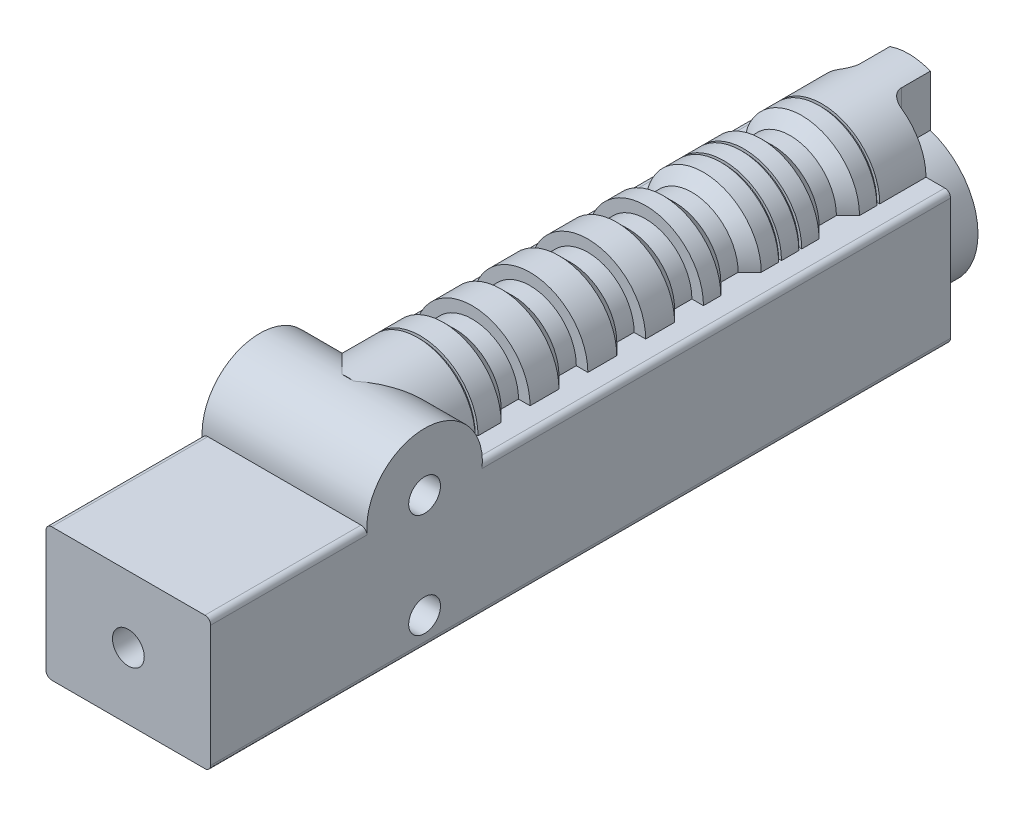
SolidWorks part; units mm, degrees
ref_plane "Front Plane" through (0, 0, 0) normal (0, 0, 1) x (1, 0, 0)
ref_plane "Top Plane" through (0, 0, 0) normal (0, 1, 0) x (1, 0, 0)
ref_plane "Right Plane" through (0, 0, 0) normal (1, 0, 0) x (0, 0, -1)
sketch "Sketch1" plane through (0, 0, 0) normal (0, 0, 1) x (1, 0, 0)
  line L1 (-14.25, -11.5) -> (14.25, -11.5)
  line L2 (-14.25, -11.5) -> (-14.25, 11.5)
  line L3 (-14.25, 11.5) -> (14.25, 11.5)
  line L4 (14.25, -11.5) -> (14.25, 11.5)
  line L5 (-14.25, -11.5) -> (14.25, 11.5) construction
  line L6 (-14.25, 11.5) -> (14.25, -11.5) construction
  point P0 (0, 0)
  dimension "D1" = 23
  dimension "D2" = 28.5
extrude "Centre block" add sketch "Sketch1" along normal blind 128
sketch "Sketch3" plane through (0, 0, 0) normal (0, 0, -1) x (-1, 0, 0)
  line L0 (-14.25, 11.5) -> (14.25, 11.5) construction
  line L1 (-10, 11.5) -> (10, 11.5)
  arc A0 (10, 11.5) -> (-10, 11.5) centre (0, 11.5) ccw
  dimension "D1" = 20
extrude "top cylinder" add sketch "Sketch3" against normal blind 90 and the other way blind 7
ref_plane "top" through (0, 11.5, 0) normal (0, 1, 0) x (1, 0, 0)
ref_axis "Axis3" through (0, 11.5, -7) along (0, 0, 1)
sketch "Sketch9" plane through (0, 11.5, 0) normal (0, 1, 0) x (1, 0, 0)
  line L0 (10, 0) -> (10, -90) construction
  line L1 (10, -78) -> (10, -81.8886)
  line L2 (10, -74.0526) -> (10, -73.5)
  line L3 (10, 0) -> (23.1871, 0)
  line L4 (23.1871, -74.0526) -> (23.1871, 0)
  line L5 (14.25, 0) -> (10, 0) construction
  line L6 (10, -8.5) -> (9.5, -8.5)
  line L7 (10, -11.5) -> (8, -13.5)
  line L8 (10, -8) -> (9.5, -8)
  line L9 (9.5, -8.5) -> (9.5, -8)
  line L10 (10, -8) -> (10, 0)
  line L11 (8, -13.5) -> (8, -16.5)
  line L12 (8, -16.5) -> (10, -18.5)
  line L13 (10, -11.5) -> (10, -8.5)
  line L14 (10, -21.5) -> (10, -18.5)
  line L15 (10, -22) -> (9.5, -22)
  line L16 (10, -25) -> (10, -22)
  line L17 (10, -21.5) -> (9.5, -21.5)
  line L18 (9.5, -22) -> (9.5, -21.5)
  line L19 (10, -25) -> (9.5, -25)
  line L20 (8, -60.3) -> (8, -58.5)
  line L21 (10, -25.5) -> (9.5, -25.5)
  line L22 (9.5, -25) -> (9.5, -25.5)
  line L23 (10, -28.5) -> (8, -30.5)
  line L24 (8, -30.5) -> (8, -33.5)
  line L25 (8, -33.5) -> (10, -35.5)
  line L26 (10, -28.5) -> (10, -25.5)
  line L27 (8, -48.5) -> (8, -51.5)
  line L28 (8, -41.5) -> (10, -43.5)
  line L29 (10, -38.5) -> (10, -35.5)
  line L30 (8, -58.5) -> (10, -58.5)
  line L31 (8, -51.5) -> (10, -53.5)
  line L34 (8, -61.5) -> (10, -63.5)
  line L35 (8, -60.3) -> (8, -61.5)
  line L36 (8, -48.5) -> (10, -48.5)
  line L37 (8, -71.5) -> (10, -73.5)
  line L38 (8, -70.3) -> (8, -71.5)
  line L39 (10, -68.5) -> (10, -63.5)
  line L40 (10, -58.5) -> (10, -53.5)
  line L41 (10, -48.5) -> (10, -43.5)
  line L42 (10, -78) -> (9.5, -78)
  line L43 (8, -41.5) -> (8, -38.5)
  line L44 (10, -74.0526) -> (10, -77.5)
  line L45 (10, -81.8886) -> (23.1871, -81.8886)
  line L46 (23.1871, -74.0526) -> (23.1871, -81.8886)
  line L47 (10, -77.5) -> (9.5, -77.5)
  line L48 (9.5, -78) -> (9.5, -77.5)
  line L52 (8, -38.5) -> (10, -38.5)
  line L54 (8, -70.3) -> (8, -68.5)
  line L55 (8, -68.5) -> (10, -68.5)
  point P52 (8, -38.5)
  dimension "D1" = 0.5
  dimension "D2" = 0.5
  dimension "D3" = 8
  dimension "D4" = 3
  dimension "D5" = 2
  dimension "D6" = 3
  dimension "D7" = 2
  dimension "D8" = 2
  dimension "D9" = 0.5
  dimension "D10" = 0.5
  dimension "D11" = 3
  dimension "D12" = 0.5
  dimension "D13" = 3
  dimension "D14" = 2
  dimension "D15" = 3
  dimension "D16" = 2
  dimension "D17" = 3
  dimension "D18" = 3
  dimension "D19" = 2
  dimension "D20" = 3
  dimension "D22" = 0.5
  dimension "D23" = 4
  dimension "D21" = 4
revolve "Cut-Revolve2" cut sketch "Sketch9" angle 180 about axis through (0, 11.5, -7) along (0, 0, 1)
sketch "Sketch4" plane through (0, 11.5, 0) normal (0, -1, 0) x (1, 0, 0)
  line L1 (10, -7) -> (-10, -7) construction
  line L3 (-3.25, -7) -> (-3.25, -2)
  line L4 (10, 0) -> (-10, 0) construction
  line L5 (-5.25, 0) -> (-10, 0)
  line L6 (-10, 0) -> (-10, -7)
  line L7 (-10, -7) -> (-10, 0) construction
  line L8 (-10, -7) -> (-3.25, -7)
  line L9 (3.75, -7) -> (3.75, -2)
  line L10 (-14.25, 0) -> (14.25, 0) construction
  line L11 (5.75, 0) -> (10, 0)
  line L12 (10, 0) -> (10, -7)
  line L13 (10, -7) -> (3.75, -7)
  arc A0 (5.75, 0) -> (3.75, -2) centre (5.75, -2) ccw
  arc A1 (-3.25, -2) -> (-5.25, 0) centre (-5.25, -2) ccw
  point P21 (3.75, 0)
  point P25 (-3.25, 0)
  dimension "D3" = 2
  dimension "D1" = 3.25
  dimension "D2" = 7
extrude "nose" cut sketch "Sketch4" against normal through all
sketch "Sketch5" plane through (14.25, 0, 0) normal (1, 0, 0) x (0, 0, -1)
  line L0 (-128, 11.5) -> (0, 11.5) construction
  line L1 (-128, -11.5) -> (-128, 11.5) construction
  line L2 (-101, 11.5) -> (-81, 11.5)
  arc A0 (-81, 11.5) -> (-101, 11.5) centre (-91, 11.5) ccw
  dimension "D1" = 20
  dimension "D2" = 37
extrude "t cross" add sketch "Sketch5" against normal up to surface (28.5 mm away) up to face at (-14.25, 0, 64)
sketch "Sketch6" plane through (0, 0, 0) normal (0, 0, -1) x (-1, 0, 0)
  line L0 (14.25, -11.5) -> (-14.25, -11.5) construction
  circle A0 centre (0, 0.5) radius 12
  dimension "D1" = 24
  dimension "D2" = 12
extrude "Barrel" add sketch "Sketch6" along normal blind 7 contours A0
ref_axis "Axis1" through (0, 0.5, -37.165) along (0, 0, 1)
sketch "Sketch2" plane through (0, 0, 0) normal (0, 0, -1) x (-1, 0, 0)
  line L0 (14.25, 11.5) -> (14.25, -11.5) construction
  line L1 (14.25, 10) -> (14.25, -10)
  arc A0 (14.25, -10) -> (14.25, 10) centre (14.25, 0) ccw
  dimension "D1" = 20
extrude "side cylinder" add sketch "Sketch2" against normal up to surface (128 mm away) up to face at (0, 0, 128)
ref_axis "side axis" through (-14.25, 0, 135.3823) along (0, 0, -1)
ref_plane "side" through (-14.25, 0, 0) normal (1, 0, 0) x (0, 0, -1)
sketch "Sketch7" plane through (-14.25, 0, 0) normal (1, 0, 0) x (0, 0, -1)
  line L0 (-51, -10) -> (-51, -9)
  line L1 (0, -10) -> (-51, -10)
  line L2 (0, -10) -> (0, -14.8124)
  line L3 (0, -14.8124) -> (-117.5, -14.8124)
  line L4 (-117.5, -14.8124) -> (-124.65, -14.8124)
  line L5 (-51, -9) -> (-51.5, -9)
  line L6 (-51.5, -9) -> (-51.5, -10)
  line L7 (-51.5, -10) -> (-55.5, -10)
  line L8 (-60.5, -10) -> (-64.5, -10)
  line L9 (-57.5, -8) -> (-55.5, -10)
  line L10 (-66.5, -8) -> (-64.5, -10)
  line L11 (-57.5, -8) -> (-58.7748, -8)
  line L12 (-58.7748, -8) -> (-60.5, -8)
  line L13 (-66.5, -8) -> (-67.7748, -8)
  line L14 (-60.5, -8) -> (-60.5, -10)
  line L15 (-75.5, -8) -> (-73.5, -10)
  line L16 (-75.5, -8) -> (-76.7748, -8)
  line L18 (-84.5, -8) -> (-82.5, -10)
  line L19 (-84.5, -8) -> (-85.7748, -8)
  line L21 (-93.5, -8) -> (-91.5, -10)
  line L22 (-93.5, -8) -> (-94.7748, -8)
  line L24 (-102.5, -8) -> (-100.5, -10)
  line L25 (-102.5, -8) -> (-105.5, -8)
  line L26 (-111, -10) -> (-114, -10)
  line L27 (-69.5, -10) -> (-73.5, -10)
  line L28 (-78.5, -10) -> (-82.5, -10)
  line L29 (-87.5, -10) -> (-91.5, -10)
  line L30 (-96.5, -10) -> (-100.5, -10)
  line L31 (-107.5, -10) -> (-110.5, -10)
  line L32 (-105.5, -8) -> (-107.5, -10)
  line L33 (-114.5, -10) -> (-117.5, -10)
  line L34 (-67.7748, -8) -> (-69.5, -8)
  line L35 (-110.5, -10) -> (-110.5, -9)
  line L36 (-110.5, -9) -> (-111, -9)
  line L37 (-111, -10) -> (-111, -9)
  line L38 (-117.5, -10) -> (-119.5, -8)
  line L39 (-114, -10) -> (-114, -9)
  line L40 (-114, -9) -> (-114.5, -9)
  line L41 (-114.5, -10) -> (-114.5, -9)
  line L42 (-119.5, -8) -> (-122.65, -8)
  line L43 (-122.65, -8) -> (-124.65, -10)
  line L45 (-69.5, -8) -> (-69.5, -10)
  line L46 (-124.65, -14.8124) -> (-124.65, -10)
  line L48 (-76.7748, -8) -> (-78.5, -8)
  line L49 (-78.5, -8) -> (-78.5, -10)
  line L53 (-85.7748, -8) -> (-87.5, -8)
  line L56 (-87.5, -8) -> (-87.5, -10)
  line L57 (-94.7748, -8) -> (-96.5, -8)
  line L58 (-96.5, -8) -> (-96.5, -10)
  point P49 (-60.5, -8)
  dimension "D1" = 51
  dimension "D2" = 0.5
  dimension "D3" = 1
  dimension "D4" = 3
  dimension "D5" = 2
  dimension "D6" = 4
  dimension "D8" = 2
  dimension "D9" = 0.5
  dimension "D10" = 0.5
  dimension "D11" = 3
  dimension "D12" = 3
  dimension "D13" = 3.15
  dimension "D14" = 3
  dimension "D15" = 2
  dimension "D16" = 2
  dimension "D17" = 4
  dimension "D7" = 6
revolve "Cut-Revolve1" cut sketch "Sketch7" angle 180 about axis through (-14.25, 0, 135.3823) along (0, 0, -1)
sketch "Sketch8" plane through (0, 0, 128) normal (0, 0, 1) x (1, 0, 0)
  circle A0 centre (0, 0) radius 2.75
  dimension "D1" = 5.5
extrude "Back hole" cut sketch "Sketch8" against normal blind 5
ref_axis "Axis5" through (-14.25, 11.5, 91) along (1, 0, 0)
sketch "Sketch15" plane through (14.25, 0, 0) normal (1, 0, 0) x (0, 0, -1)
  circle A0 centre (-91, 11.5) radius 2.75
  circle A1 centre (-91, -6.5) radius 2.75
  dimension "D1" = 5.5
  dimension "D3" = 18
  dimension "D2" = 2
extrude "Cut-Extrude6" cut sketch "Sketch15" against normal blind 10
sketch "Sketch16" plane through (0, 0, -7) normal (0, 0, -1) x (-1, 0, 0)
  circle A0 centre (0, 0) radius 6.5
  dimension "D1" = 13
fillet "Fillet2" radius 1 6 edges at (14.25, -11.5, 64) (-14.25, -11.5, 64) (-14.25, 11.5, 40.5) (-14.25, 11.5, 114.5) (14.25, 11.5, 40.5) (14.25, 11.5, 114.5)
extrude "Cut-Extrude7" cut sketch "Sketch16" against normal blind 20
sketch "Sketch17" [suppressed] plane through (0, 0, 0) normal (0, 0, -1) x (-1, 0, 0)
  line L0 (14.25, 12.65) -> (14.25, -12.65) construction
  line L1 (14.25, -11.5) -> (21.8493, -11.5)
  line L2 (14.25, -11.5) -> (14.25, -6.5)
  line L3 (14.25, -6.5) -> (21.8493, -6.5)
  line L4 (21.8493, -11.5) -> (21.8493, -6.5)
  line L5 (13.25, -11.5) -> (0, -11.5) construction
  arc A0 (14.25, -10) -> (14.25, 10) centre (14.25, 0) ccw construction
  dimension "D1" = 5
extrude "Boss-Extrude1" [suppressed] add sketch "Sketch17" against normal blind 0.3
pattern_linear "LPattern1" [suppressed] count 11 spacing 5.07 of bodies 120
sketch "Sketch18" [suppressed] plane through (0, 0, 51.5) normal (0, 0, -1) x (-1, 0, 0)
  line L0 (14.25, 12.65) -> (14.25, -12.65) construction
  line L1 (14.25, -11.4537) -> (21.8493, -11.4537)
  line L2 (14.25, -11.4537) -> (14.25, -6.5)
  line L3 (14.25, -6.5) -> (21.8493, -6.5)
  line L4 (21.8493, -11.4537) -> (21.8493, -6.5)
  line L5 (21.8493, -11.5) -> (21.8493, -6.5) construction
  arc A0 (21.8493, -6.5) -> (14.25, 10) centre (14.25, 0) ccw construction
extrude "Boss-Extrude2" [suppressed] add sketch "Sketch18" against normal blind 0.3
pattern_linear "LPattern2" [suppressed] count 2 spacing 3.7 of bodies 122
pattern_linear "LPattern3" [suppressed] count 6 spacing 9 of bodies 123
sketch "Sketch19" [suppressed] plane through (0, 0, 110.5) normal (0, 0, 1) x (1, 0, 0)
  line L1 (-14.25, -11.4537) -> (-21.8493, -11.4537)
  line L2 (-14.25, -11.4537) -> (-14.25, -6.5)
  line L3 (-14.25, -6.5) -> (-21.8493, -6.5)
  line L4 (-21.8493, -11.4537) -> (-21.8493, -6.5)
extrude "Boss-Extrude3" [suppressed] add sketch "Sketch19" along normal blind 0.3 from offset 2.95 offset against normal yes
pattern_linear "LPattern4" [suppressed] count 2 spacing 2.6 of bodies 125
pattern_linear "LPattern5" [suppressed] count 3 spacing 3.5 of bodies 126
pattern_linear "LPattern6" [suppressed] count 2 spacing 17.5 of bodies 127
sketch "Sketch20" [suppressed] plane through (0, 0, -7) normal (0, 0, -1) x (-1, 0, 0)
  line L0 (13.25, -11.5) -> (0, -11.5) construction
  line L1 (-11.9896, 0) -> (-6.4896, 0)
  line L2 (-11.9896, 0) -> (-11.9896, -11.5)
  line L3 (-11.9896, -11.5) -> (12, -11.5)
  line L4 (12, 0) -> (12, -11.5)
  line L5 (6.5, 0) -> (12, 0)
  arc A0 (-4.7958, 11.5) -> (0, -11.5) centre (0, 0.5) ccw construction
  arc A1 (-6.4896, 0) -> (6.5, 0) centre (0.0052, 0) ccw
extrude "Boss-Extrude4" [suppressed] add sketch "Sketch20" against normal blind 0.3
pattern_linear "LPattern7" [suppressed] count 2 spacing 3.5 along (0, 0, 1) of bodies 129
sketch "Sketch21" plane through (-14.25, 0, 0) normal (-1, 0, 0) x (0, 0, 1)
  line L1 (-12.1946, 24.7848) -> (140.3905, 24.7848)
  line L2 (-12.1946, 24.7848) -> (-12.1946, -18.054)
  line L3 (-12.1946, -18.054) -> (140.3905, -18.054)
  line L4 (140.3905, 24.7848) -> (140.3905, -18.054)
extrude "Cut-Extrude10" cut sketch "Sketch21" along normal through all
sketch "Sketch23" plane through (-14.25, 0, 0) normal (-1, 0, 0) x (0, 0, 1)
  line L0 (135.3823, 0) -> (-12.8715, 0) construction
  line L1 (128, 10.5) -> (128, -10.5) construction
  line L2 (0, 10.5) -> (0, -10.5) construction
  circle A0 centre (10, 0) radius 2.75
  circle A1 centre (118, 0) radius 2.75
  circle A2 centre (64, 0) radius 2.75
  dimension "D1" = 5.5
  dimension "D2" = 5.5
  dimension "D3" = 5.5
  dimension "D4" = 10
  dimension "D5" = 10
  dimension "D6" = 54
  dimension "D7" = 54
extrude "Cut-Extrude11" cut sketch "Sketch23" against normal blind 5
sketch "Sketch24" plane through (0, -11.5, 0) normal (0, -1, 0) x (1, 0, 0)
  line L0 (0, -7) -> (0, 90) construction
  line L1 (0, 0) -> (13.25, 0) construction
  circle A0 centre (0, 20) radius 2.75
  circle A1 centre (0, 90) radius 2.75
  dimension "D1" = 5.5
  dimension "D2" = 5.5
  dimension "D3" = 20
  dimension "D4" = 70
extrude "Bottom Mount Holes" cut sketch "Sketch24" against normal blind 5
